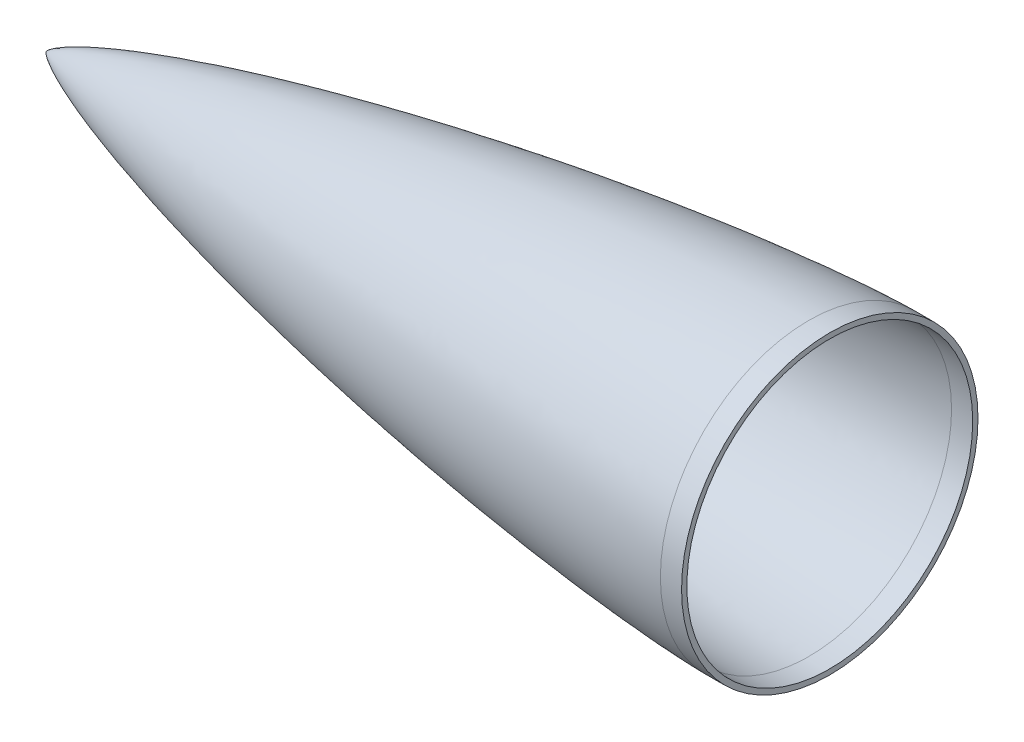
SolidWorks part; units mm, degrees
ref_plane "Front Plane" through (0, 0, 0) normal (0, 0, 1) x (1, 0, 0)
ref_plane "Top Plane" through (0, 0, 0) normal (0, 1, 0) x (1, 0, 0)
ref_plane "Right Plane" through (0, 0, 0) normal (1, 0, 0) x (0, 0, -1)
sketch "Sketch1" plane through (0, 0, 0) normal (0, 0, 1) x (1, 0, 0)
  line L0 (0, 0) -> (457.2, 0) construction
  line L1 (0, 0) -> (0, 88.9) construction
  line L2 (457.2, 88.9) -> (457.2, 0) construction
  line L3 (457.2, 0) -> (0, 0)
  line L5 (457.2, 0) -> (469.9, 0)
  line L7 (457.2, 88.9) -> (469.9, 88.9)
  line L8 (469.9, 0) -> (469.9, 88.9)
  spline S0 degree 4 poles (0, 0) (0.0023, 0.0117) (0.0082, 0.0346) (0.0259, 0.0787) (0.0695, 0.163) (0.1339, 0.2631) (0.2191, 0.3779) (0.337, 0.5207) (0.5083, 0.7099) (0.7967, 0.9963) (1.2974, 1.437) (2.1714, 2.1155) (3.7007, 3.1561) (6.4159, 4.7683) (11.1362, 7.1982) (18.8825, 10.6592) (32.1618, 15.8286) (51.2292, 22.2419) (75.2304, 29.3379) (102.9883, 36.6578) (131.6198, 43.512) (160.3745, 49.8273) (189.2277, 55.6742) (218.164, 61.0945) (247.1725, 66.1133) (276.2458, 70.7417) (305.3786, 74.9797) (334.5673, 78.8147) (363.8094, 82.22) (389.4419, 84.7797) (411.4452, 86.618) (428.6335, 87.7745) (439.7385, 88.3707) (448.4263, 88.7187) (453.4393, 88.8519) (455.9463, 88.8945) (457.2, 88.9) knots 0 0 0 0 0 0.000101 0.000202 0.000405 0.000809 0.001116 0.001422 0.001985 0.002988 0.004584 0.007113 0.011426 0.01877 0.031526 0.052412 0.083828 0.140383 0.203215 0.266046 0.328877 0.391708 0.454539 0.51737 0.580202 0.643033 0.705864 0.768695 0.831526 0.894357 0.925773 0.957189 0.978594 0.989297 1 1 1 1 1 construction
  spline S1 degree 4 poles (0, 0) (0.0023, 0.0117) (0.0082, 0.0346) (0.0259, 0.0787) (0.0695, 0.163) (0.1339, 0.2631) (0.2191, 0.3779) (0.337, 0.5207) (0.5083, 0.7099) (0.7967, 0.9963) (1.2974, 1.437) (2.1714, 2.1155) (3.7007, 3.1561) (6.4159, 4.7683) (11.1362, 7.1982) (18.8825, 10.6592) (32.1618, 15.8286) (51.2292, 22.2419) (75.2304, 29.3379) (102.9883, 36.6578) (131.6198, 43.512) (160.3745, 49.8273) (189.2277, 55.6742) (218.164, 61.0945) (247.1725, 66.1133) (276.2458, 70.7417) (305.3786, 74.9797) (334.5673, 78.8147) (363.8094, 82.22) (389.4419, 84.7797) (411.4452, 86.618) (428.6335, 87.7745) (439.7385, 88.3707) (448.4263, 88.7187) (453.4393, 88.8519) (455.9463, 88.8945) (457.2, 88.9) knots 0 0 0 0 0 0.000101 0.000202 0.000405 0.000809 0.001116 0.001422 0.001985 0.002988 0.004584 0.007113 0.011426 0.01877 0.031526 0.052412 0.083828 0.140383 0.203215 0.266046 0.328877 0.391708 0.454539 0.51737 0.580202 0.643033 0.705864 0.768695 0.831526 0.894357 0.925773 0.957189 0.978594 0.989297 1 1 1 1 1
  dimension "D1" = 457.2
  dimension "D2" = 88.9
  dimension "D3" = 12.7
revolve "Revolve1" add sketch "Sketch1" angle 360 about L3
shell "Shell1" thickness 3.175 removed face at (469.9, 0, -88.9)
